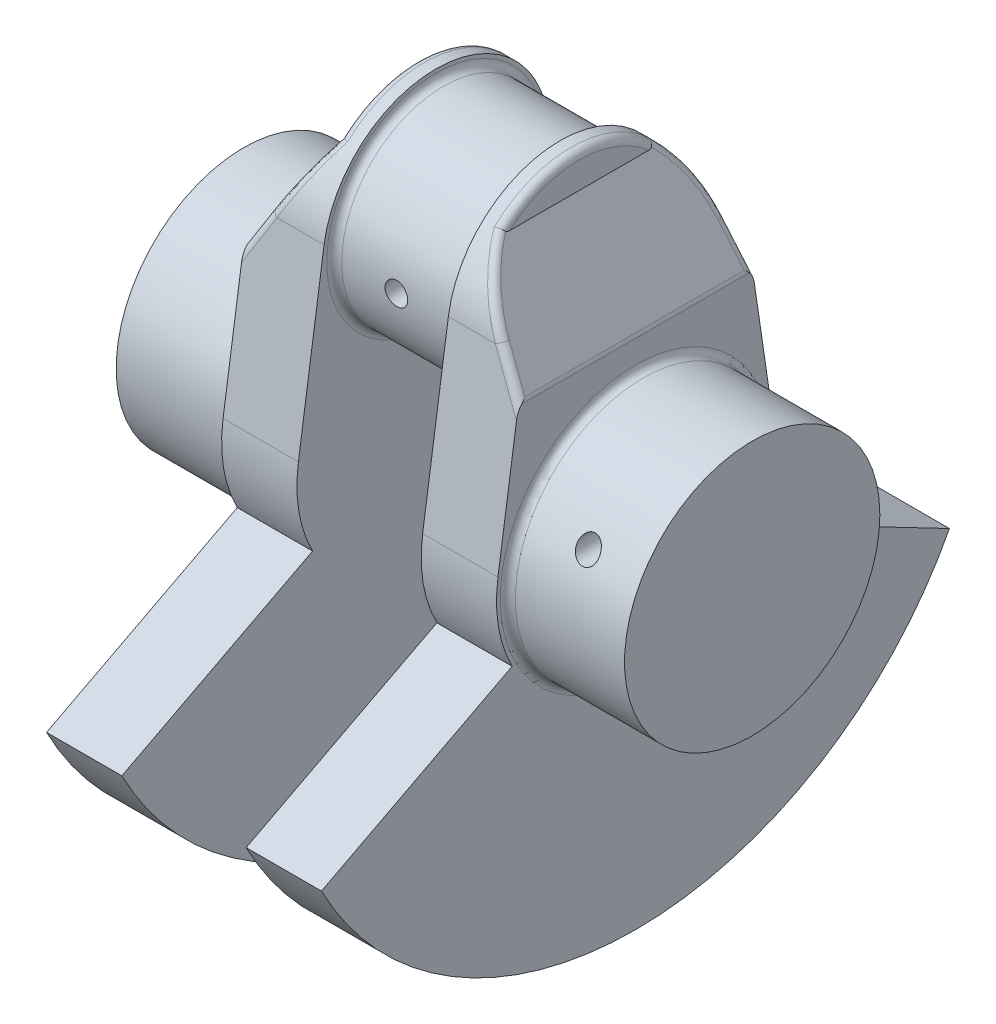
SolidWorks part; units mm, degrees
ref_plane "Спереди" through (0, 0, 0) normal (0, 0, 1) x (1, 0, 0)
ref_plane "Сверху" through (0, 0, 0) normal (0, 1, 0) x (1, 0, 0)
ref_plane "Справа" through (0, 0, 0) normal (1, 0, 0) x (0, 0, -1)
sketch "Эскиз3" plane through (0, 0, 0) normal (1, 0, 0) x (0, 0, -1)
  circle A0 centre (0, 0) radius 33.9
  dimension "D1" = 67.8
extrude "Бобышка-Вытянуть1" add sketch "Эскиз3" along normal blind 31 contours A0
sketch "Эскиз4" plane through (31, 0, 0) normal (1, 0, 0) x (0, 0, -1)
  line L0 (-29.6818, 51.8579) -> (-36.5086, 5.3602)
  line L1 (29.6818, 51.8579) -> (36.5086, 5.3602)
  line L2 (-83.379, -43.4044) -> (0, 0)
  line L3 (0, -47) -> (0, 0)
  line L4 (83.379, -43.4044) -> (0, 0)
  circle A0 centre (0, 0) radius 36.9
  circle A1 centre (0, 47.5) radius 30
  circle A2 centre (0, 0) radius 33.9 construction
  arc A3 (83.379, -43.4044) -> (-83.379, -43.4044) centre (0, 0) cw
  circle M1 centre (0, 0) radius 33.9
  dimension "D1" = 47.5
  dimension "D2" = 60
  dimension "D4" = 94
  dimension "D3" = 3
  dimension "D5" = 117.5
extrude "Бобышка-Вытянуть2" add sketch "Эскиз4" along normal blind 20 contours A1 A0 | A0 A1 M1 | A1 M1 | A1 A0 L1 | A1 A0 M1 | A1 M1 | A1 L0 A0 | A0 | L4 A3 L2 region at (31, 28.8579, 30.213) region at (31, 53.1931, 0) region at (31, 28.8579, -30.213) region at (31, 36.4222, 0) region at (31, 2.6521, -36.3209) region at (31, 25.8071, 0) region at (31, 5.6798, 0)
sketch "Эскиз6" plane through (0, 0, 0) normal (0, 0, 1) x (1, 0, 0)
  line L0 (31, 77.5) -> (46, 77.5)
  line L1 (51, 77.5) -> (31, 77.5) construction
  line L2 (46, 77.5) -> (46, 68.5)
  line L3 (46, 68.5) -> (31, 42.5192)
  line L4 (31, 77.5) -> (31, 51.8579) construction
  line L5 (31, 42.5192) -> (31, 77.5)
  dimension "D1" = 5
  dimension "D2" = 60
  dimension "D3" = 9
extrude "Вырез-Вытянуть1" cut sketch "Эскиз6" against normal through all and the other way through all
fillet "Скругление1" radius 2 6 edges at (31, 42.5192, 0) (33.6958, 47.1886, -30.3673) (41.5742, 60.8343, -26.8737) (33.6958, 47.1886, 30.3673) (41.5742, 60.8343, 26.8737) (46, 77.5, 0)
sketch "Эскиз5" plane through (51, 0, 0) normal (1, 0, 0) x (0, 0, -1)
  circle A1 centre (0, 47.5) radius 27
  dimension "D1" = 54
  dimension "D2" = 47.5
extrude "Бобышка-Вытянуть3" add sketch "Эскиз5" along normal blind 16.5
fillet "Скругление2" radius 2 1 edges at (51, 47.5, -27)
fillet "Скругление3" radius 2 1 edges at (31, 0, -33.9)
ref_axis "Ось1" through (67.5, -102.575, 0) along (0, 1, 0)
mirror "Зеркальное отражение4" about plane through (67.5, 47.5, 0) normal (1, 0, 0) of bodies 103 111
sketch "Эскиз10" plane through (0, 0, 0) normal (0, 0, 1) x (1, 0, 0)
  line L0 (67.5, 74.5) -> (67.5, 20.5)
  line L1 (82, 74.5) -> (53, 74.5) construction
  line L2 (53, 20.5) -> (82, 20.5) construction
  circle A0 centre (67.5, 47.5) radius 3
extrude "Вырез-Вытянуть3" cut sketch "Эскиз10" against normal through all both and the other way through all contours A0
ref_axis "Ось8" through (67.5, 47.5, -27) along (0, 0, 1)
ref_plane "Плоскость10" through (37.4431, 64.8534, 0) normal (-0.5, -0.866, 0) x (0, 0, 1)
ref_axis "Ось9" through (42.2817, 62.0598, 32.0212) along (0, 0, -1)
sketch "Эскиз12" plane through (4.8386, -2.7936, 0) normal (-0.866, 0.5, 0) x (0, 0, 1)
  line L0 (-29.1101, 52.8586) -> (29.1101, 52.8586)
  line L1 (29.1101, 52.8586) -> (27.703, 63.9253) construction
  line L2 (-29.1101, 52.8586) -> (29.1101, 52.8586) construction
  line L3 (-32.0212, 74.8862) -> (32.0212, 74.8862) construction
  circle A0 centre (0, 74.8862) radius 2.95
  point P4 (0, 0)
  point P14 (0, 0)
  point P15 (0, 0)
extrude "Вырез-Вытянуть5" cut sketch "Эскиз12" against normal offset from surface (95 mm away) 95 contours A0 region at (42.2817, 62.0598, 0) up to face at (40.1452, 58.3592, 0.0296)
ref_axis "Ось10" through (185.9193, -20.8694, 0) along (-0.866, 0.5, 0)
ref_plane "Плоскость11" through (121, 0, 0) normal (1, 0, 0) x (0, 0, -1)
ref_axis "Ось12" through (121, 16.6118, -32.0212) along (0, 0, 1)
ref_plane "Плоскость13" through (0, 0, 0) normal (0, 0, 1) x (1, 0, 0)
sketch "Эскиз14" plane through (0, 0, 0) normal (0, 0, 1) x (1, 0, 0)
  line L0 (121, -91.7169) -> (121, 91.7169) construction
  line L1 (9.712, 80.8639) -> (65.1742, 48.8428) construction
  circle A0 centre (121, 16.6118) radius 3
extrude "Вырез-Вытянуть6" cut sketch "Эскиз14" against normal through all both and the other way through all
